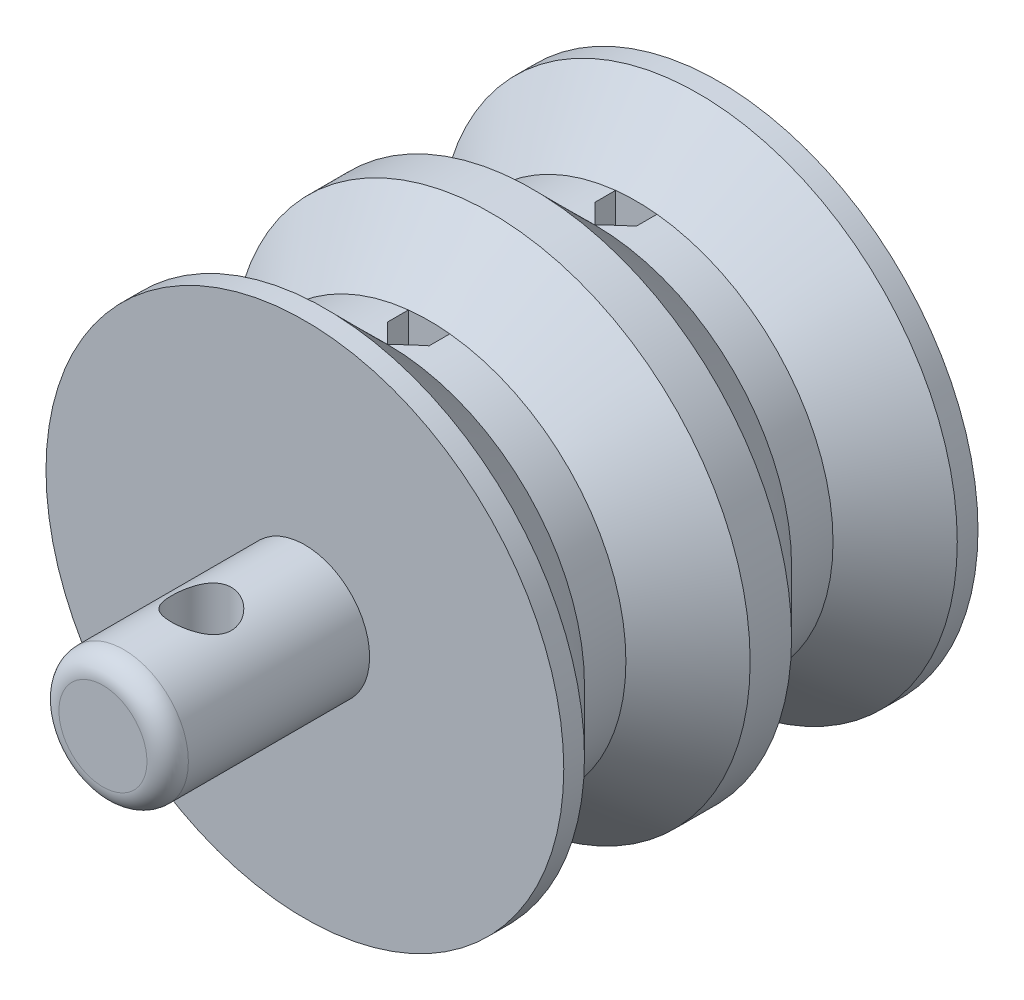
SolidWorks part; units mm, degrees
ref_plane "Plan de face" through (0, 0, 0) normal (0, 0, 1) x (1, 0, 0)
ref_plane "Plan de dessus" through (0, 0, 0) normal (0, 1, 0) x (1, 0, 0)
ref_plane "Plan de droite" through (0, 0, 0) normal (1, 0, 0) x (0, 0, -1)
sketch "Esquisse1" plane through (0, 0, 0) normal (0, 0, 1) x (1, 0, 0)
  circle A0 centre (0, 0) radius 3.125
  dimension "D1" = 6.25
extrude "Boss.-Extru.1" add sketch "Esquisse1" along normal blind 9.75
fillet "Congé1" radius 1 1 edges at (3.125, 0, 9.75)
sketch "Esquisse2" plane through (0, 0, 0) normal (0, 0, -1) x (-1, 0, 0)
  circle A0 centre (0, 0) radius 12.5
  dimension "D1" = 25
extrude "Boss.-Extru.3" add sketch "Esquisse2" along normal blind 20
sketch "Esquisse5" plane through (0, 0, 0) normal (1, 0, 0) x (0, 0, -1)
  line L0 (1, 12.5) -> (4, 9.5)
  line L1 (20, 12.5) -> (0, 12.5) construction
  line L2 (4, 9.5) -> (6, 9.5)
  line L3 (6, 9.5) -> (9, 12.5)
  line L4 (9, 12.5) -> (1, 12.5)
  line L5 (0, 0) -> (20, 0) construction
  line L6 (20, -12.5) -> (20, 12.5) construction
  line L7 (10, 0) -> (10, 12.5) construction
  line L8 (0, 12.5) -> (1, 12.5) construction
  line L9 (9, 12.5) -> (10, 12.5) construction
  line L10 (11, 12.5) -> (19, 12.5)
  line L11 (14, 9.5) -> (11, 12.5)
  line L12 (19, 12.5) -> (16, 9.5)
  line L13 (16, 9.5) -> (14, 9.5)
  dimension "D1" = 45
  dimension "D2" = 2
  dimension "D3" = 1
revolve "Enlèvement de matière-Révolution1" cut sketch "Esquisse5" angle 360 about L5
sketch "Esquisse6" plane through (0, 0, 0) normal (0, 1, 0) x (1, 0, 0)
  line L0 (0, -8.75) -> (0, 0) construction
  circle A0 centre (0, -5) radius 1.45
  point P2 (0, 0)
  dimension "D1" = 2.9
  dimension "D2" = 5
extrude "Enlèv. mat.-Extru.1" cut sketch "Esquisse6" against normal through all both and the other way through all
ref_plane "Plan1" through (0, 9.5, 0) normal (0, 1, 0) x (1, 0, 0)
sketch "Esquisse7" plane through (0, 9.5, 0) normal (0, 1, 0) x (1, 0, 0)
  line L0 (-1, 15) -> (0, 14)
  line L1 (-1, 16) -> (1, 16)
  line L2 (-1, 16) -> (-1, 15)
  line L3 (-1, 15) -> (1, 15)
  line L4 (1, 16) -> (1, 15)
  line L5 (-1, 16) -> (1, 15) construction
  line L6 (-1, 15) -> (1, 16) construction
  line L7 (0, 14) -> (1, 15)
  line L8 (0, 16) -> (0, 14) construction
  line L9 (1.6297, 14) -> (1.6297, 16) construction
  line L10 (9.5, 14) -> (-9.5, 14) construction
  line L11 (9.5, 16) -> (-9.5, 16) construction
  point P0 (0, 15.5)
  point P14 (1.6297, 15)
  point P15 (0, 15)
  dimension "D1" = 2
  dimension "D2" = 1
  dimension "D3" = 135
extrude "Enlèv. mat.-Extru.2" cut sketch "Esquisse7" against normal through all both and the other way through all contours L4 L1 L2 L3 | L0 L7 L3 region at (0, 9.5, -14.6667) region at (0, 9.5, -15.5)
pattern_linear "Répétition linéaire1" count 2 spacing 10 along (0, 0, 1) of "Enlèv. mat.-Extru.2"
